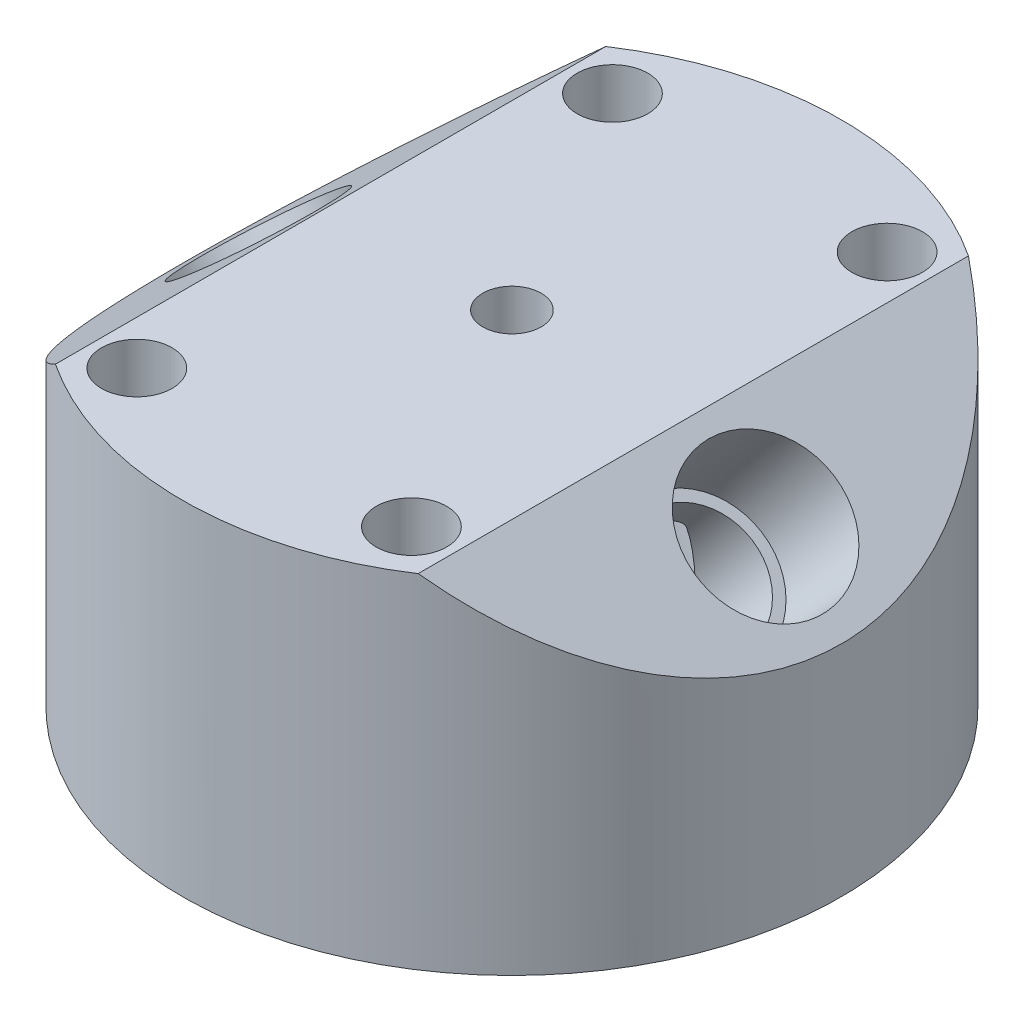
SolidWorks part; units mm, degrees
material "AISI 304"
ref_plane "Front Plane" through (0, 0, 0) normal (0, 0, 1) x (1, 0, 0)
ref_plane "Top Plane" through (0, 0, 0) normal (0, 1, 0) x (1, 0, 0)
ref_plane "Right Plane" through (0, 0, 0) normal (1, 0, 0) x (0, 0, -1)
sketch "MASTER" plane through (0, 0, 0) normal (0, 0, 1) x (1, 0, 0)
  line L0 (0, 0) -> (0, 38.1) construction
  line L1 (0, 38.1) -> (-30.48, 38.1)
  line L2 (-30.48, 38.1) -> (-30.48, 0)
  line L3 (-30.48, 0) -> (-12.7, 0)
  line L4 (-12.7, 0) -> (-12.7, 19.05)
  line L5 (-6.3246, 19.05) -> (-4.7625, 17.4879)
  line L6 (-4.7625, 17.4879) -> (0, 17.4879)
  line L7 (-6.3246, 19.05) -> (-12.7, 19.05)
  line L8 (-12.7, 0) -> (0, 0) construction
  line L9 (0, 38.1) -> (0, 17.4879)
  line L10 (33.1516, -30.216) -> (-31.067, 46.3167) construction
  line L11 (21.713, -38.7917) -> (-42.0021, 37.1411) construction
  line L12 (-7.4178, 18.1327) -> (-6.3246, 19.05) construction
  line L13 (-11.6068, 0.9173) -> (-12.7, 0) construction
  line L14 (-36.5346, 41.7289) -> (-21.8455, 24.2232) construction
  line L15 (-31.067, 46.3167) -> (-42.0021, 37.1411) construction
  dimension "D1" = 6.3754
  dimension "D2" = 38.1
  dimension "D3" = 60.96
  dimension "D4" = 25.4
  dimension "D5" = 19.05
  dimension "D6" = 9.525
  dimension "D7" = 135
  dimension "D8" = 14.2748
  dimension "D9" = 50
revolve "MASTER_SKETCH" add sketch "MASTER" angle 360 about L9
sketch "Sketch2" plane through (0, 0, 0) normal (0, 0, 1) x (1, 0, 0)
  line L0 (-30.48, 20.2483) -> (-9.2051, 38.1)
  line L1 (-30.48, 38.1) -> (-30.48, 0) construction
  line L3 (0, 38.1) -> (-30.48, 38.1) construction
  line L4 (21.713, -38.7917) -> (-42.0021, 37.1411) construction
  line L5 (-30.48, 20.2483) -> (-30.48, 38.1)
  line L6 (-30.48, 38.1) -> (-9.2051, 38.1)
  line L7 (0, 0) -> (0, 44.6314) construction
  line L8 (30.48, 38.1) -> (9.2051, 38.1)
  line L9 (30.48, 20.2483) -> (30.48, 38.1)
  line L10 (30.48, 20.2483) -> (9.2051, 38.1)
  dimension "D1" = 2.032
extrude "Cut-Extrude1" cut sketch "Sketch2" against normal through all both and the other way through all
hole_wizard "1/4-28 Tapped Hole1" positions "Sketch3" profile "Sketch4" tap size "1/4-28" standard "ANSI Inch" end condition through all
sketch "Sketch3" plane through (0, 38.1, 0) normal (0, 1, 0) x (1, 0, 0)
  point P0 (0, 0)
sketch "Sketch4" plane through (0, 38.1, 0) normal (1, 0, 0) x (0, 0, 1)
  line L0 (0, 0) -> (0, 38.1)
  line L1 (0, 38.1) -> (2.7051, 38.1)
  line L2 (2.7051, 38.1) -> (2.7051, 0)
  line L5 (2.7051, 0) -> (0, 0)
  line L11 (0, -6.35) -> (0, 107.95) construction
  dimension "Thru Tap Drill Dia." = 5.4102
  dimension "Thru Tap Drill Depth" = 38.1
cosmetic thread "Hole Thread1" parameters "D2"=6.35
sketch "Sketch5" plane through (0, 38.1, 0) normal (0, 1, 0) x (1, 0, 0)
  circle A0 centre (0, 0) radius 30.48
  dimension "D1" = 60.96
extrude "Cut-Extrude2" cut sketch "Sketch5" against normal blind 6.35
fillet "use-round-corner-endmill" radius 0.762 2 edges at (-6.3246, 19.05, 0) (-12.7, 19.05, 0)
hole_wizard "1/4 NPT Tapped Hole1" positions "Sketch6" profile "Sketch7" size "1/4" standard "ANSI Inch" end condition through all
sketch "Sketch6" plane through (-22.5639, 26.8906, 0) normal (-0.6428, 0.766, 0) x (0.766, 0.6428, 0)
  point P0 (-1.1643, 0)
sketch "Sketch7" plane through (-23.4558, 26.1423, 0) normal (0, 0, 1) x (-0.766, -0.6428, 0)
  line L0 (0, 0) -> (0, 54.6954)
  line L1 (0, 54.6954) -> (5.5626, 54.6954)
  line L2 (-6.558, 9.906) -> (-6.8546, 0) construction
  line L3 (5.5626, 54.6954) -> (5.5626, 9.906)
  line L4 (5.5626, 9.906) -> (6.558, 9.906)
  line L5 (6.558, 9.906) -> (6.8546, 0)
  line L7 (6.8546, 0) -> (0, 0)
  line L8 (0, -6.35) -> (0, 107.95) construction
  line L11 (-5.5626, 9.906) -> (-6.558, 9.906) construction
  dimension "Thru Tap Drill Dia." = 11.1252
  dimension "Thru Tap Drill Depth" = 54.6954
  dimension "Thread Dia." = 13.7092
  dimension "Thread Angle" = 3.43
  dimension "Thread Depth" = 9.906
mirror "Mirror1" about plane through (0, 0, 0) normal (1, 0, 0) of "1/4 NPT Tapped Hole1"
hole_wizard "1/4 Clearance Hole1" positions "Sketch9" profile "Sketch10" hole size "1/4" standard "ANSI Inch" end condition through all
sketch "Sketch9" plane through (0, 31.75, 0) normal (0, 1, 0) x (1, 0, 0)
  line L1 (12.7, -21.997) -> (25.4, 0)
  line L2 (25.4, 0) -> (12.7, 21.997)
  line L3 (12.7, 21.997) -> (-12.7, 21.997)
  line L4 (-12.7, 21.997) -> (-25.4, 0)
  line L5 (-25.4, 0) -> (-12.7, -21.997)
  line L6 (-12.7, -21.997) -> (12.7, -21.997)
  circle A0 centre (0, 0) radius 25.4 construction
  point P3 (12.7, -21.997)
  point P5 (12.7, 21.997)
  point P6 (-12.7, 21.997)
  point P8 (-12.7, -21.997)
  dimension "D1" = 50.8
sketch "Sketch10" plane through (-12.7, 31.75, 21.997) normal (1, 0, 0) x (0, 0, 1)
  line L0 (0, 0) -> (0, 31.75)
  line L1 (0, 31.75) -> (3.2639, 31.75)
  line L2 (3.2639, 31.75) -> (3.2639, 0)
  line L5 (3.2639, 0) -> (0, 0)
  line L11 (0, -6.35) -> (0, 107.95) construction
  dimension "Thru Hole Dia." = 6.5278
  dimension "Thru Hole Depth" = 31.75
